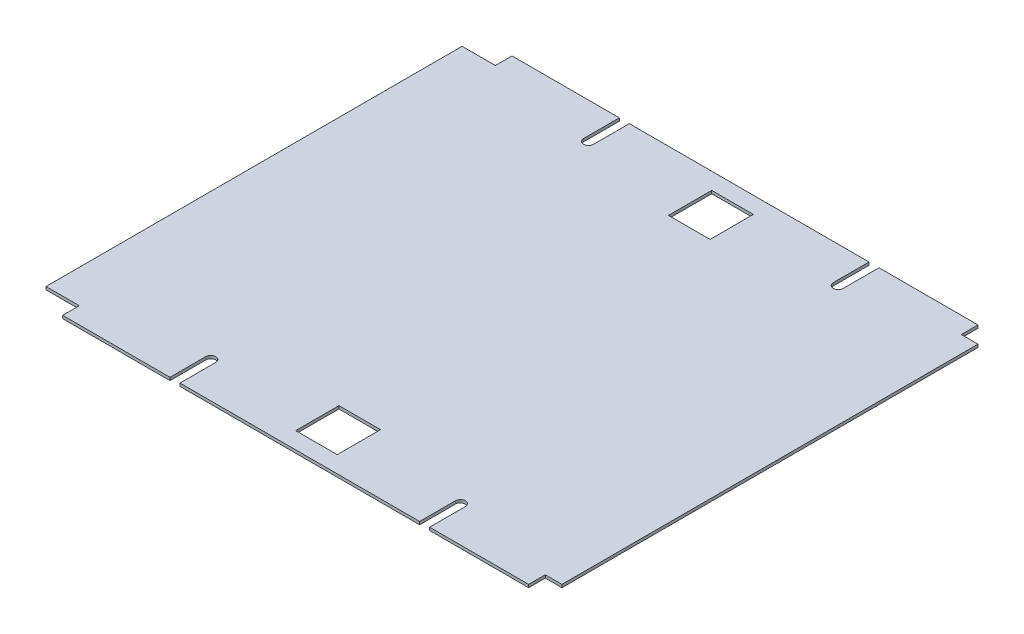
SolidWorks part; units mm, degrees
ref_plane "Front Plane" through (0, 0, 0) normal (0, 0, 1) x (1, 0, 0)
ref_plane "Top Plane" through (0, 0, 0) normal (0, 1, 0) x (1, 0, 0)
ref_plane "Right Plane" through (0, 0, 0) normal (1, 0, 0) x (0, 0, -1)
sketch "Sketch1" plane through (0, 0, 0) normal (0, 1, 0) x (1, 0, 0)
  line L1 (-280, 270) -> (280, 270)
  line L2 (-320, 250) -> (-320, -250)
  line L3 (-280, -270) -> (280, -270)
  line L4 (320, 250) -> (320, -250)
  line L5 (-280, 253.125) -> (280, -253.125) construction
  line L6 (-280, -253.125) -> (280, 253.125) construction
  line L9 (-320, 250) -> (-280, 250)
  line L10 (-280, 270) -> (-280, 250)
  line L13 (320, 250) -> (280, 250)
  line L14 (280, 270) -> (280, 250)
  line L17 (320, -250) -> (280, -250)
  line L18 (280, -270) -> (280, -250)
  line L21 (-320, -250) -> (-280, -250)
  line L22 (-280, -270) -> (-280, -250)
  point P0 (0, 0)
  dimension "D2" = 540
  dimension "D3" = 40
  dimension "D4" = 20
  dimension "D5" = 20
  dimension "D6" = 40
  dimension "D7" = 40
  dimension "D8" = 20
  dimension "D9" = 20
  dimension "D10" = 40
  dimension "D11" = 640
extrude "Boss-Extrude1" add sketch "Sketch1" along normal blind 3.5
sketch "Sketch2" plane through (0, 3.5, 0) normal (0, 1, 0) x (1, 0, 0)
  line L0 (-280, -270) -> (280, -270) construction
  line L1 (30, -250) -> (-20, -250)
  line L2 (30, -250) -> (30, -198)
  line L3 (30, -198) -> (-20, -198)
  line L4 (-20, -250) -> (-20, -198)
  line L6 (280, 270) -> (-280, 270) construction
  line L7 (-20, 198) -> (30, 198)
  line L8 (-20, 198) -> (-20, 250)
  line L9 (-20, 250) -> (30, 250)
  line L10 (30, 198) -> (30, 250)
  line L12 (320, -250) -> (320, 250) construction
  line L14 (320, 250) -> (300, 250)
  line L15 (320, 250) -> (320, 210)
  line L16 (320, 210) -> (300, 210)
  line L17 (300, 250) -> (300, 210)
  line L18 (320, -250) -> (300, -250)
  line L19 (320, -250) -> (320, -210)
  line L20 (320, -210) -> (300, -210)
  line L21 (300, -250) -> (300, -210)
  dimension "D1" = 52
  dimension "D2" = 50
  dimension "D3" = 20
  dimension "D4" = 290
  dimension "D5" = 50
  dimension "D6" = 52
  dimension "D7" = 20
  dimension "D8" = 290
  dimension "D9" = 40
  dimension "D10" = 20
  dimension "D11" = 40
  dimension "D12" = 20
extrude "Cut-Extrude1" cut sketch "Sketch2" against normal blind 10
sketch "Sketch3" plane through (0, 3.5, 0) normal (0, 1, 0) x (1, 0, 0)
  line L0 (300, 250) -> (300, 210) construction
  line L1 (280, 270) -> (-280, 270) construction
  line L2 (320, 0) -> (0, 0) construction
  line L4 (149, 227) -> (149, 270)
  line L5 (149, 270) -> (161, 270)
  line L6 (161, 227) -> (161, 270)
  line L7 (320, -210) -> (320, 210) construction
  line L8 (5, 198) -> (5, -198) construction
  line L9 (-20, 198) -> (30, 198) construction
  line L10 (30, -198) -> (-20, -198) construction
  line L11 (161, -227) -> (161, -270)
  line L12 (149, -270) -> (161, -270)
  line L13 (149, -227) -> (149, -270)
  line L14 (-139, -227) -> (-139, -270)
  line L15 (-139, -270) -> (-151, -270)
  line L16 (-151, -227) -> (-151, -270)
  line L17 (-151, 227) -> (-151, 270)
  line L18 (-139, 270) -> (-151, 270)
  line L19 (-139, 227) -> (-139, 270)
  arc A0 (149, 227) -> (161, 227) centre (155, 227) ccw
  arc A1 (149, -227) -> (161, -227) centre (155, -227) cw
  arc A2 (-139, -227) -> (-151, -227) centre (-145, -227) ccw
  arc A3 (-139, 227) -> (-151, 227) centre (-145, 227) cw
  dimension "D1" = 145
  dimension "D2" = 43
  dimension "D3" = 12
extrude "Cut-Extrude2" cut sketch "Sketch3" against normal blind 10
sketch "Sketch4" plane through (0, 3.5, 0) normal (0, 1, 0) x (1, 0, 0)
  line L1 (320, 210) -> (300, 210)
  line L2 (320, 210) -> (320, -210)
  line L3 (320, -210) -> (300, -210)
  line L4 (300, 210) -> (300, -210)
extrude "Cut-Extrude3" cut sketch "Sketch4" against normal through all
